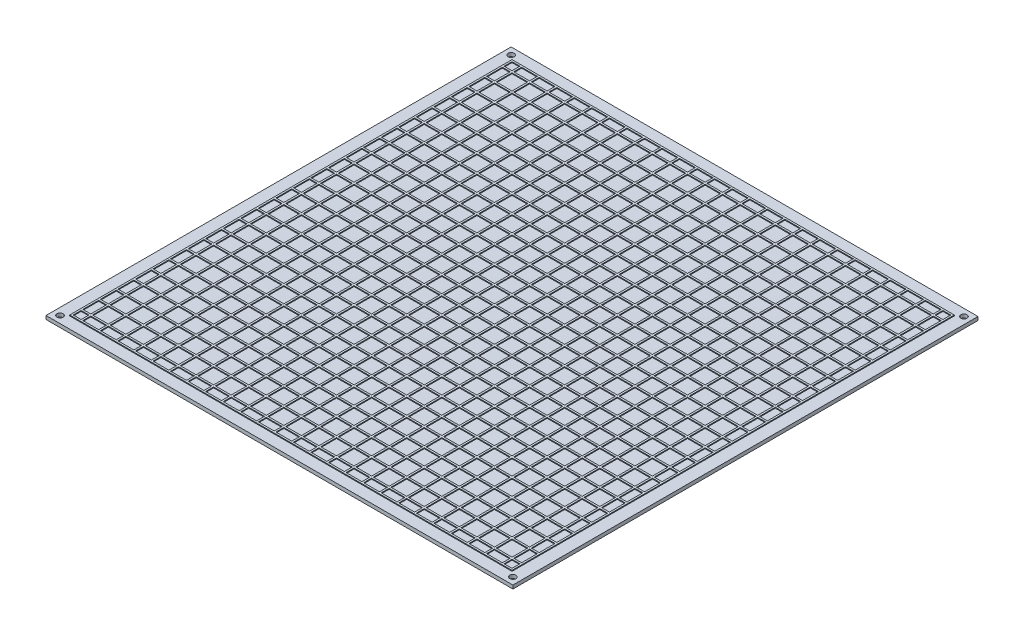
SolidWorks part; units mm, degrees
other "Камера1"
ref_plane "Спереди" through (0, 0, 0) normal (0, 0, 1) x (1, 0, 0)
ref_plane "Сверху" through (0, 0, 0) normal (0, 1, 0) x (1, 0, 0)
ref_plane "Справа" through (0, 0, 0) normal (1, 0, 0) x (0, 0, -1)
sketch "Эскиз1" plane through (0, 0, 0) normal (0, 1, 0) x (1, 0, 0)
  line L0 (0, 0) -> (0, 132.5) construction
  line L5 (-133, 132.5) -> (133, 132.5)
  line L6 (-133, 132.5) -> (-133, -132.5)
  line L7 (-133, -132.5) -> (133, -132.5)
  line L8 (133, 132.5) -> (133, -132.5)
  line L9 (-133, 132.5) -> (133, -132.5) construction
  line L10 (-133, -132.5) -> (133, 132.5) construction
  line L11 (0, 0) -> (-133, 0) construction
  circle A0 centre (-129, 128.5) radius 1.75
  circle A1 centre (129, 128.5) radius 1.75
  circle A2 centre (129, -128.5) radius 1.75
  circle A3 centre (-129, -128.5) radius 1.75
  point P1 (0, 0)
  dimension "D3" = 129
  dimension "D4" = 4
  dimension "D1" = 3.5
  dimension "D2" = 128.5
  dimension "D5" = 4
extrude "Бобышка-Вытянуть1" add sketch "Эскиз1" along normal blind 2
sketch "Esboço1" plane through (0, 2, 0) normal (0, 1, 0) x (1, 0, 0)
  line L0 (-126, 126) -> (126, 126)
  line L1 (-125, -125) -> (-120.5, -125)
  line L2 (-125, -125) -> (-125, 125)
  line L3 (-125, 125) -> (-120.5, 125)
  line L4 (125, -125) -> (125, 125)
  line L5 (-125, -125) -> (125, 125) construction
  line L6 (-125, 125) -> (125, -125) construction
  line L7 (126, -126) -> (126, 126)
  line L8 (-126, -126) -> (126, -126)
  line L9 (-126, -126) -> (-126, 126)
  line L10 (0, 126) -> (0, -126) construction
  line L11 (-0.5, 125) -> (-0.5, -125)
  line L12 (0.5, 125) -> (0.5, -125)
  line L13 (0.5, 126) -> (0.5, -126) construction
  line L14 (-0.5, 126) -> (-0.5, -126) construction
  line L15 (0.5, -125) -> (9.5, -125)
  line L16 (-125, -125) -> (125, -125) construction
  line L17 (0.5, 125) -> (9.5, 125)
  line L18 (-125, 125) -> (125, 125) construction
  line L19 (10.5, 125) -> (10.5, -125)
  line L20 (9.5, 125) -> (9.5, -125)
  line L21 (20.5, 125) -> (20.5, -125)
  line L22 (19.5, 125) -> (19.5, -125)
  line L23 (30.5, 125) -> (30.5, -125)
  line L24 (29.5, 125) -> (29.5, -125)
  line L25 (40.5, 125) -> (40.5, -125)
  line L26 (39.5, 125) -> (39.5, -125)
  line L27 (50.5, 125) -> (50.5, -125)
  line L28 (49.5, 125) -> (49.5, -125)
  line L29 (60.5, 125) -> (60.5, -125)
  line L30 (59.5, 125) -> (59.5, -125)
  line L31 (70.5, 125) -> (70.5, -125)
  line L32 (69.5, 125) -> (69.5, -125)
  line L33 (80.5, 125) -> (80.5, -125)
  line L34 (79.5, 125) -> (79.5, -125)
  line L35 (90.5, 125) -> (90.5, -125)
  line L36 (89.5, 125) -> (89.5, -125)
  line L37 (100.5, 125) -> (100.5, -125)
  line L38 (99.5, 125) -> (99.5, -125)
  line L39 (110.5, 125) -> (110.5, -125)
  line L40 (109.5, 125) -> (109.5, -125)
  line L41 (-110.5, 125) -> (-110.5, -125)
  line L42 (-109.5, 125) -> (-109.5, -125)
  line L43 (-100.5, 125) -> (-100.5, -125)
  line L44 (-99.5, 125) -> (-99.5, -125)
  line L45 (-90.5, 125) -> (-90.5, -125)
  line L46 (-89.5, 125) -> (-89.5, -125)
  line L47 (-80.5, 125) -> (-80.5, -125)
  line L48 (-79.5, 125) -> (-79.5, -125)
  line L49 (-69.5, 125) -> (-69.5, -125)
  line L50 (-70.5, 125) -> (-70.5, -125)
  line L51 (-60.5, 125) -> (-60.5, -125)
  line L52 (-59.5, 125) -> (-59.5, -125)
  line L53 (-50.5, 125) -> (-50.5, -125)
  line L54 (-49.5, 125) -> (-49.5, -125)
  line L55 (-40.5, 125) -> (-40.5, -125)
  line L56 (-39.5, 125) -> (-39.5, -125)
  line L57 (-30.5, 125) -> (-30.5, -125)
  line L58 (-29.5, 125) -> (-29.5, -125)
  line L59 (-20.5, 125) -> (-20.5, -125)
  line L60 (-19.5, 125) -> (-19.5, -125)
  line L61 (-10.5, 125) -> (-10.5, -125)
  line L62 (-9.5, 125) -> (-9.5, -125)
  line L63 (-126, 126) -> (126, 126) construction
  line L64 (-109.5, 125) -> (-100.5, 125)
  line L65 (-99.5, 125) -> (-90.5, 125)
  line L66 (-89.5, 125) -> (-80.5, 125)
  line L67 (-79.5, 125) -> (-70.5, 125)
  line L68 (-69.5, 125) -> (-60.5, 125)
  line L69 (-59.5, 125) -> (-50.5, 125)
  line L70 (-49.5, 125) -> (-40.5, 125)
  line L71 (-39.5, 125) -> (-30.5, 125)
  line L72 (-29.5, 125) -> (-20.5, 125)
  line L73 (-19.5, 125) -> (-10.5, 125)
  line L74 (-9.5, 125) -> (-0.5, 125)
  line L75 (10.5, 125) -> (19.5, 125)
  line L76 (20.5, 125) -> (29.5, 125)
  line L77 (30.5, 125) -> (39.5, 125)
  line L78 (40.5, 125) -> (49.5, 125)
  line L79 (50.5, 125) -> (59.5, 125)
  line L80 (60.5, 125) -> (69.5, 125)
  line L81 (70.5, 125) -> (79.5, 125)
  line L82 (80.5, 125) -> (89.5, 125)
  line L83 (90.5, 125) -> (99.5, 125)
  line L84 (100.5, 125) -> (109.5, 125)
  line L85 (110.5, 125) -> (119.5, 125)
  line L86 (-109.5, -125) -> (-100.5, -125)
  line L87 (-99.5, -125) -> (-90.5, -125)
  line L88 (-89.5, -125) -> (-80.5, -125)
  line L89 (-79.5, -125) -> (-70.5, -125)
  line L90 (-69.5, -125) -> (-60.5, -125)
  line L91 (-59.5, -125) -> (-50.5, -125)
  line L92 (-49.5, -125) -> (-40.5, -125)
  line L93 (-39.5, -125) -> (-30.5, -125)
  line L94 (-29.5, -125) -> (-20.5, -125)
  line L95 (-19.5, -125) -> (-10.5, -125)
  line L96 (-9.5, -125) -> (-0.5, -125)
  line L97 (10.5, -125) -> (19.5, -125)
  line L98 (20.5, -125) -> (29.5, -125)
  line L99 (30.5, -125) -> (39.5, -125)
  line L100 (40.5, -125) -> (49.5, -125)
  line L101 (50.5, -125) -> (59.5, -125)
  line L102 (60.5, -125) -> (69.5, -125)
  line L103 (70.5, -125) -> (79.5, -125)
  line L104 (80.5, -125) -> (89.5, -125)
  line L105 (90.5, -125) -> (99.5, -125)
  line L106 (100.5, -125) -> (109.5, -125)
  line L107 (110.5, -125) -> (119.5, -125)
  line L108 (-120.5, 125) -> (-120.5, -125)
  line L109 (-119.5, 125) -> (-119.5, -125)
  line L110 (-119.5, 125) -> (-110.5, 125)
  line L111 (-119.5, -125) -> (-110.5, -125)
  line L112 (120.5, 125) -> (120.5, -125)
  line L113 (119.5, 125) -> (119.5, -125)
  line L114 (120.5, -125) -> (125, -125)
  line L115 (120.5, 125) -> (125, 125)
  point P0 (0, 0)
  dimension "D1" = 250
  dimension "D2" = 250
  dimension "D4" = 0.5
  dimension "D3" = 1
  dimension "D5" = 0.5
  dimension "D6" = 12
  dimension "D7" = 2
  dimension "D8" = 2
extrude "Ressalto-extrusão1" add sketch "Esboço1" along normal blind 0.5
sketch "Esboço2" plane through (0, 2, 0) normal (0, 1, 0) x (1, 0, 0)
  line L0 (-126, 0) -> (126, 0) construction
  line L3 (-126, -0.5) -> (126, -0.5)
  line L4 (-126, 0.5) -> (126, 0.5)
  line L5 (-126, 10.5) -> (126, 10.5)
  line L6 (-126, 9.5) -> (126, 9.5)
  line L7 (-126, 20.5) -> (126, 20.5)
  line L8 (-126, 19.5) -> (126, 19.5)
  line L9 (-126, 30.5) -> (126, 30.5)
  line L10 (-126, 29.5) -> (126, 29.5)
  line L11 (-126, 40.5) -> (126, 40.5)
  line L12 (-126, 39.5) -> (126, 39.5)
  line L13 (-126, 50.5) -> (126, 50.5)
  line L14 (-126, 49.5) -> (126, 49.5)
  line L15 (-126, 60.5) -> (126, 60.5)
  line L16 (-126, 59.5) -> (126, 59.5)
  line L17 (-126, 70.5) -> (126, 70.5)
  line L18 (-126, 69.5) -> (126, 69.5)
  line L19 (-126, 80.5) -> (126, 80.5)
  line L20 (-126, 79.5) -> (126, 79.5)
  line L21 (-126, 90.5) -> (126, 90.5)
  line L22 (-126, 89.5) -> (126, 89.5)
  line L23 (-126, 100.5) -> (126, 100.5)
  line L24 (-126, 99.5) -> (126, 99.5)
  line L25 (-126, 110.5) -> (126, 110.5)
  line L26 (-126, 109.5) -> (126, 109.5)
  line L27 (-126, 120.5) -> (126, 120.5)
  line L28 (-126, 119.5) -> (126, 119.5)
  line L29 (-126, -119.5) -> (126, -119.5)
  line L30 (-126, -120.5) -> (126, -120.5)
  line L31 (-126, -109.5) -> (126, -109.5)
  line L32 (-126, -110.5) -> (126, -110.5)
  line L33 (-126, -99.5) -> (126, -99.5)
  line L34 (-126, -100.5) -> (126, -100.5)
  line L35 (-126, -89.5) -> (126, -89.5)
  line L36 (-126, -90.5) -> (126, -90.5)
  line L37 (-126, -79.5) -> (126, -79.5)
  line L38 (-126, -80.5) -> (126, -80.5)
  line L39 (-126, -69.5) -> (126, -69.5)
  line L40 (-126, -70.5) -> (126, -70.5)
  line L41 (-126, -59.5) -> (126, -59.5)
  line L42 (-126, -60.5) -> (126, -60.5)
  line L43 (-126, -49.5) -> (126, -49.5)
  line L44 (-126, -50.5) -> (126, -50.5)
  line L45 (-126, -39.5) -> (126, -39.5)
  line L46 (-126, -40.5) -> (126, -40.5)
  line L47 (-126, -29.5) -> (126, -29.5)
  line L48 (-126, -30.5) -> (126, -30.5)
  line L49 (-126, -19.5) -> (126, -19.5)
  line L50 (-126, -20.5) -> (126, -20.5)
  line L51 (-126, -9.5) -> (126, -9.5)
  line L52 (-126, -10.5) -> (126, -10.5)
  line L53 (-126, 120.5) -> (-126, 119.5)
  line L54 (126, 126) -> (126, 119.5)
  line L55 (-133, 0.5) -> (133, 0.5) construction
  line L56 (-133, 0) -> (133, 0) construction
  line L57 (-133, -0.5) -> (133, -0.5) construction
  line L58 (126, 110.5) -> (126, 109.5)
  line L59 (126, 100.5) -> (126, 99.5)
  line L60 (126, 90.5) -> (126, 89.5)
  line L61 (126, 80.5) -> (126, 79.5)
  line L62 (126, 70.5) -> (126, 69.5)
  line L63 (126, 60.5) -> (126, 59.5)
  line L64 (126, 50.5) -> (126, 49.5)
  line L65 (126, 40.5) -> (126, 39.5)
  line L66 (126, 30.5) -> (126, 29.5)
  line L67 (126, 20.5) -> (126, 19.5)
  line L68 (126, 10.5) -> (126, 9.5)
  line L69 (126, 0.5) -> (126, -0.5)
  line L70 (126, -9.5) -> (126, -10.5)
  line L71 (126, -19.5) -> (126, -20.5)
  line L72 (126, -29.5) -> (126, -30.5)
  line L73 (126, -39.5) -> (126, -40.5)
  line L74 (126, -49.5) -> (126, -50.5)
  line L75 (126, -59.5) -> (126, -60.5)
  line L76 (126, -69.5) -> (126, -70.5)
  line L77 (126, -79.5) -> (126, -80.5)
  line L78 (126, -89.5) -> (126, -90.5)
  line L79 (126, -99.5) -> (126, -100.5)
  line L80 (126, -109.5) -> (126, -110.5)
  line L81 (126, -119.5) -> (126, -120.5)
  line L82 (-126, -119.5) -> (-126, -120.5)
  line L83 (-126, -109.5) -> (-126, -110.5)
  line L84 (-126, -99.5) -> (-126, -100.5)
  line L85 (-126, -89.5) -> (-126, -90.5)
  line L86 (-126, -79.5) -> (-126, -80.5)
  line L87 (-126, -69.5) -> (-126, -70.5)
  line L88 (-126, -59.5) -> (-126, -60.5)
  line L89 (-126, -49.5) -> (-126, -50.5)
  line L90 (-126, -39.5) -> (-126, -40.5)
  line L91 (-126, -29.5) -> (-126, -30.5)
  line L92 (-126, -9.5) -> (-126, -10.5)
  line L93 (-126, 0.5) -> (-126, -0.5)
  line L94 (-126, 10.5) -> (-126, 9.5)
  line L95 (-126, 20.5) -> (-126, 19.5)
  line L96 (-126, 30.5) -> (-126, 29.5)
  line L97 (-126, 40.5) -> (-126, 39.5)
  line L98 (-126, 50.5) -> (-126, 49.5)
  line L99 (-126, 60.5) -> (-126, 59.5)
  line L100 (-126, 70.5) -> (-126, 69.5)
  line L101 (-126, -19.5) -> (-126, -20.5)
  line L102 (-126, 110.5) -> (-126, 109.5)
  line L103 (-126, 100.5) -> (-126, 99.5)
  line L104 (-126, 90.5) -> (-126, 89.5)
  line L105 (-126, 80.5) -> (-126, 79.5)
  line L106 (-126, 126) -> (-126, -126) construction
  point P2 (-126, 120)
  line M2 (-125, 125) -> (-125, -125)
  dimension "D1" = 0.5
  dimension "D2" = 0.5
  dimension "D3" = 13
extrude "Ressalto-extrusão4" add sketch "Esboço2" along normal blind 0.5 contours L30 L29 M2 | L29 L82 L30 M2 | L81 L29 L30 | L80 L31 L32 | L31 L83 L32 M2 | L32 L31 M2 | L79 L33 L34 | L34 L33 M2 | L78 L35 L36 | L36 L35 M2 | L35 L85 L36 M2 | L77 L37 L38 | L38 L37 M2 | L37 L86 L38 M2 | L39 L87 L40 M2 | L40 L39 M2 | L76 L39 L40 | L75 L41 L42 | L42 L41 M2 | L73 L45 L46 | L46 L45 M2 | L45 L90 L46 M2 | L72 L47 L48 | L48 L47 M2 | L47 L91 L48 M2 | L71 L49 L50 | L70 L51 L52 | L52 L51 M2 | L50 L49 M2 | L69 L4 L3 | L4 L3 M2 | L6 L5 M2 | L68 L5 L6 | L67 L7 L8 | L10 L9 M2 | L66 L9 L10 | L12 L11 M2 | L65 L11 L12 | L54 L27 L28 | L28 L27 M2 | L26 L25 M2 | L59 L23 L24 | L61 L19 L20 | L20 L19 M2 | L62 L17 L18 | L18 L17 M2 | L63 L15 L16 | L64 L13 L14 | L14 L13 M2 | L84 L34 L79 L33 | L88 L42 L75 L41 | L89 L44 L74 L43 | L8 L67 L7 L95 | L27 L53 L28 L54 | L25 L58 L26 L102 | L24 L59 L23 L103 | L21 L60 L22 L104 | L15 L63 L16 L99 region at (0.5, 2, -120) region at (0.5, 2, -110) region at (0.5, 2, -100) region at (0.5, 2, -80) region at (0.5, 2, -70) region at (0.5, 2, -60) region at (0.5, 2, -50) region at (0.5, 2, -40) region at (0.5, 2, -30) region at (0.5, 2, -20) region at (0.5, 2, -10) region at (0.5, 2, 120) region at (-125.5, 2, 120) region at (0.5, 2, 110) region at (-125.5, 2, 110) region at (0.5, 2, 100) region at (0.5, 2, 90) region at (-125.5, 2, 90) region at (0.5, 2, 80) region at (-125.5, 2, 80) region at (0.5, 2, 70) region at (-125.5, 2, 70) region at (0.5, 2, 60) region at (0.5, 2, 40) region at (-125.5, 2, 40) region at (0.5, 2, 30) region at (-125.5, 2, 30) region at (0.5, 2, 20) region at (0.5, 2, 10) region at (0.5, 2, 0)
